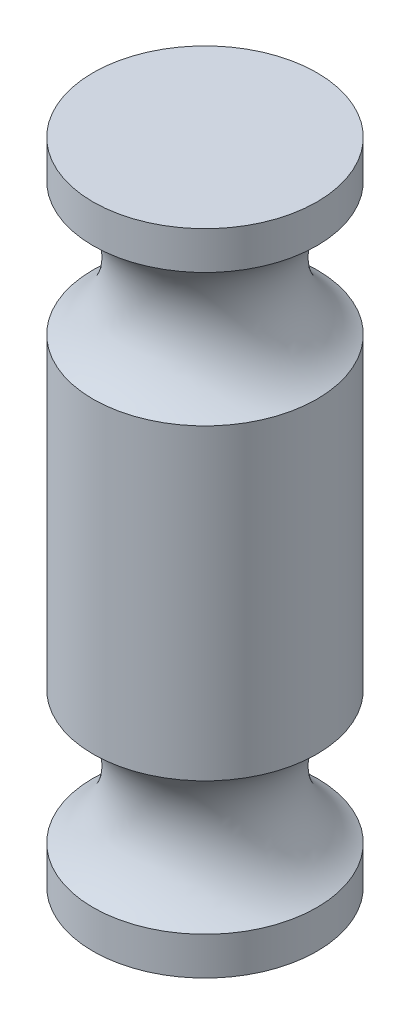
SolidWorks part; units mm, degrees
ref_plane "前视基准面" through (0, 0, 0) normal (0, 0, 1) x (1, 0, 0)
ref_plane "上视基准面" through (0, 0, 0) normal (0, 1, 0) x (1, 0, 0)
ref_plane "右视基准面" through (0, 0, 0) normal (1, 0, 0) x (0, 0, -1)
sketch "草图1" plane through (0, 0, 0) normal (0, 0, 1) x (1, 0, 0)
  line L0 (0, 0) -> (0, 8.56)
  line L1 (0, 8.56) -> (2.95, 8.56)
  line L2 (2.95, 8.56) -> (2.95, 7.56)
  line L3 (2.95, 4.06) -> (2.95, -4.04)
  line L4 (2.95, -7.54) -> (2.95, -8.54)
  line L5 (2.95, -8.54) -> (0, -8.54)
  line L6 (0, -8.54) -> (0, 0)
  arc A0 (2.95, 7.56) -> (2.95, 4.06) centre (3.9182, 5.81) ccw
  arc A1 (2.95, -4.04) -> (2.95, -7.54) centre (3.9182, -5.79) ccw
  dimension "D6" = 2
  dimension "D8" = 2
  dimension "D7" = 3.5
  dimension "D1" = 2.95
  dimension "D2" = 1
  dimension "D3" = 1
  dimension "D4" = 17.1
  dimension "D5" = 8.56
  dimension "D9" = 3.5
  dimension "D10" = 8.1
revolve "旋转1" add sketch "草图1" angle 360 about L6
